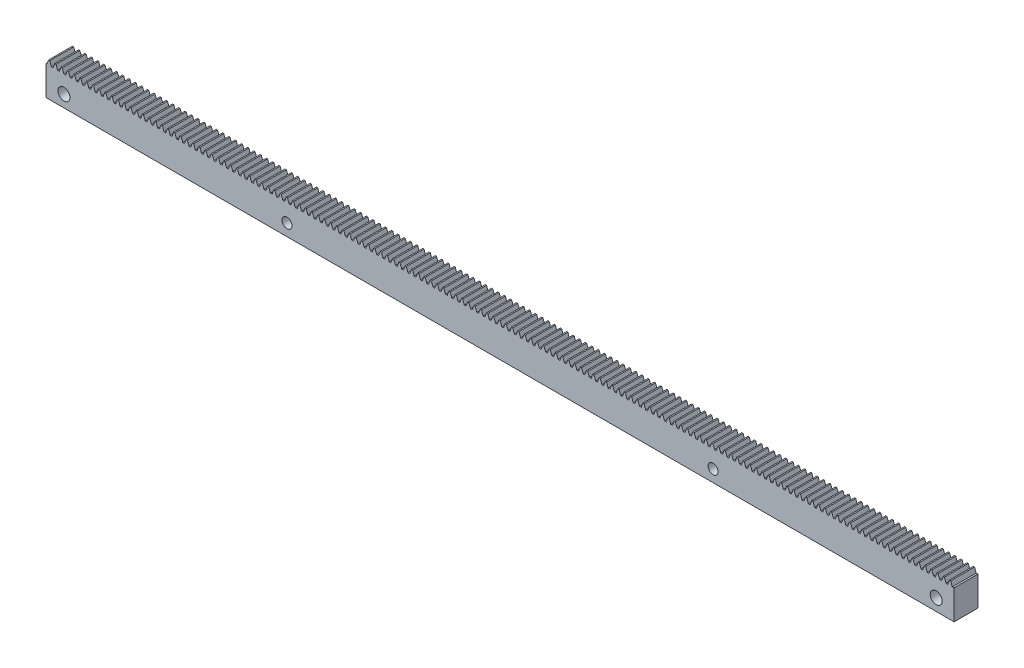
SolidWorks part; units mm, degrees
extrude "Blank" add sketch "BlankSke" against normal blind 6
sketch "BlankSke" plane through (0, 0, 0) normal (0, 0, 1) x (1, 0, 0)
  line L1 (0, 0) -> (228, 0)
  line L2 (0, 0) -> (0, 8.5)
  line L3 (0, 8.5) -> (228, 8.5)
  line L4 (228, 0) -> (228, 8.5)
  dimension "Length" = 228
material "ABS PC"
ref_plane "Plane1" through (0, 0, 0) normal (0, 0, 1) x (1, 0, 0)
ref_plane "Plane2" through (0, 0, 0) normal (0, 1, 0) x (1, 0, 0)
ref_plane "Plane3" through (0, 0, 0) normal (1, 0, 0) x (0, 0, -1)
sketch "HoldingSke" plane through (0, 0, 0) normal (0, 1, 0) x (1, 0, 0)
  line L0 (0, 0) -> (0.2783, 1.9805)
  line L1 (-15, 0) -> (100, 0) construction
  line L2 (0, 0) -> (-2.1039, 2.3779)
  line L3 (0, 0) -> (-11.863, 4.5341)
  line L4 (0, 0) -> (-4.8292, 7.1596)
  line L5 (0, 0) -> (-23.7986, -8.8762)
  line L6 (0, 0) -> (-10.5278, -7.1032)
  line L9 (-71.009, 38.7566) -> (109.412, 104.4245)
  line L10 (-76.2, 2.8779) -> (-68.2, 2.8779)
  line L11 (0, 0) -> (-4, 0)
  line L12 (-76.2, 101.6) -> (-76.181, 101.6)
  line L13 (24.9733, 27.94) -> (52.9518, 28.4284)
  line L14 (24.9733, 27.94) -> (24.9743, 27.94)
  line L15 (24.9733, 27.94) -> (100.4006, 29.5858)
  circle A0 centre (0, 0) radius 19.05
  circle A1 centre (0, 0) radius 4
  circle A2 centre (0, 0) radius 12.7
  dimension "Num_teeth" = 124
  dimension "Width" = 4
  dimension "Pitch_height" = 8
sketch "TooCutSkeIll" plane through (0, 0, 0) normal (0, 0, 1) x (1, 0, 0)
  line L0 (-0.6269, 8.4868) -> (-0.2524, 7.4579)
  line L1 (-0.134, 7.375) -> (0.134, 7.375)
  line L2 (0.2524, 7.4579) -> (0.6269, 8.4868)
  line L3 (228, 8.5) -> (0, 8.5) construction
  line L4 (0, 0) -> (0, 64.897) construction
  line L5 (-13.208, 8) -> (12.954, 8) construction
  line L6 (0, 0) -> (228, 0) construction
  line L7 (0.4497, 8) -> (0.4497, 48.7463) construction
  line L8 (-0.4497, 8) -> (-0.4497, 48.7463) construction
  line L9 (0.6457, 8.5) -> (0.6457, 8.5254)
  line L10 (-0.6457, 8.5) -> (-0.6457, 8.5254)
  line L11 (-0.6457, 8.5254) -> (0.6457, 8.5254)
  arc A0 (0.134, 7.375) -> (0.2524, 7.4579) centre (0.134, 7.501) ccw
  arc A1 (-0.2524, 7.4579) -> (-0.134, 7.375) centre (-0.134, 7.501) ccw
  arc A2 (0.6457, 8.5) -> (0.6269, 8.4868) centre (0.6457, 8.48) ccw
  arc A3 (-0.6269, 8.4868) -> (-0.6457, 8.5) centre (-0.6457, 8.48) ccw
  dimension "Addendum_plus" = 0.5254
  dimension "Pitch_height" = 8
  dimension "Pressure_angle" = 20
  dimension "Gap_width" = 0.8994
  dimension "Dedendum" = 0.625
extrude "ToothCutIll" [suppressed] cut sketch "TooCutSkeIll" against normal through all
sketch "TooCutSkeSim" plane through (0, 0, 0) normal (0, 0, 1) x (1, 0, 0)
  line L0 (0.2222, 7.375) -> (-0.2222, 7.375)
  line L1 (0.6409, 8.5254) -> (0.2222, 7.375)
  line L2 (0, 17.4625) -> (0, 53.467) construction
  line L3 (0.6409, 8.5254) -> (-0.6409, 8.5254)
  line L6 (-0.6409, 8.5254) -> (-0.2222, 7.375)
  line L9 (-0.4497, 8) -> (0.4497, 8) construction
  line L10 (0, 0) -> (228, 0) construction
  line L11 (0.4497, 8) -> (0.4497, 53.467) construction
  line L12 (-0.4497, 8) -> (-0.4497, 53.467) construction
  dimension "Addendum_plus" = 0.5254
  dimension "Pitch_height" = 8
  dimension "Pressure_angle" = 20
  dimension "Gap_width" = 0.8994
  dimension "Dedendum" = 0.625
extrude "ToothCutSim" cut sketch "TooCutSkeSim" against normal through all
pattern_linear "TeethCuts" count 146 spacing 1.5708 along (1, 0, 0) of "ToothCutSim"
sketch "Sketch1" plane through (0, 0, 0) normal (0, 0, 1) x (1, 0, 0)
  line L0 (223.5, 0) -> (223.5, 3) construction
  line L1 (0, 0) -> (228, 0) construction
  line L2 (228, 3) -> (186.6573, 3) construction
  line L3 (228, 0) -> (228, 7.4088) construction
  line L4 (114, 0) -> (114, -6.8538) construction
  line L5 (0, 7.375) -> (0, 0) construction
  line L6 (4.5, 3) -> (223.5, 3) construction
  circle A0 centre (223.5, 3) radius 1.5
  circle A1 centre (4.5, 3) radius 1.5
  circle A2 centre (60.5157, 3) radius 1.25
  circle A3 centre (167.4843, 3) radius 1.25
  dimension "D3" = 3
  dimension "D6" = 3
  dimension "D1" = 3
  dimension "D7" = 2.5
  dimension "D2" = 4.5
  dimension "D4" = 4.5
  dimension "D5" = 3
extrude "Cut-Extrude1" cut sketch "Sketch1" against normal blind 10
equation "' \"Module@HoldingSke\" = 6.35"
equation "' \"Num_teeth@HoldingSke\" = 12"
equation "' \"Ap@HoldingSke\" =  20"
equation "' \"Ap@HoldingSke\" = 20"
equation "' \"Width@HoldingSke\" = 0.25 * 25.4"
equation "' \"Show_teeth@HoldingSke\" = 500"
equation "' \"Backlash@HoldingSke\" = 0.009 * 25.4"
equation "' \"Addendum_fac@HoldingSke\" = 1.0"
equation "' \"Dedendum_fac@HoldingSke\" = 1.25"
equation "' \"Dedendum_add@HoldingSke\" = 0.00005 * 25.4"
equation "' \"Clearance_fac@HoldingSke\" = 0.25"
equation "' \"Pitch_height@HoldingSke\" = 1 * 25.4"
equation "' \"Length@HoldingSke\" = 4.71 * 25.4"
equation "\"Pitch@HoldingSke\" = 1 / \"Module@HoldingSke\""
equation "\"MPH@HoldingSke\" = \"Dedendum_fac@HoldingSke\" / \"Pitch@HoldingSke\" + 2 * \"Dedendum_add@HoldingSke\" + 0.002 * 25.4"
equation "\"MPH@HoldingSke\" = ((sgn( \"MPH@HoldingSke\" - \"Pitch_height@HoldingSke\")+1)*( \"MPH@HoldingSke\" - \"Pitch_height@HoldingSke\"))/2 + \"Pitch_height@HoldingSke\""
equation "\"Blank_height@BlankSke\" = \"Pitch_height@HoldingSke\" + \"Addendum_fac@HoldingSke\"  / \"Pitch@HoldingSke\" "
equation "\"Length@BlankSke\"=\"Length@HoldingSke\"+36"
equation "\"Pressure_angle@TooCutSkeIll\" = \"Ap@HoldingSke\""
equation "\"Addendum_plus@TooCutSkeIll\" =  \"Addendum_fac@HoldingSke\"  / \"Pitch@HoldingSke\" + 0.001 *25.4"
equation "\"Dedendum@TooCutSkeIll\" = \"Dedendum_fac@HoldingSke\"  / \"Pitch@HoldingSke\""
equation "\"Pitch_height@TooCutSkeIll\" =  \"MPH@HoldingSke\""
equation "\"Gap_width@TooCutSkeIll\" = 3.14159265 / 2 / \"Pitch@HoldingSke\" + 6 * \"Backlash@HoldingSke\""
equation "\"Pressure_angle@TooCutSkeSim\" = \"Ap@HoldingSke\""
equation "\"Addendum_plus@TooCutSkeSim\" =  \"Addendum_fac@HoldingSke\"  / \"Pitch@HoldingSke\" + 0.001 * 25.4"
equation "\"Dedendum@TooCutSkeSim\" = \"Dedendum_fac@HoldingSke\"  / \"Pitch@HoldingSke\""
equation "\"Pitch_height@TooCutSkeSim\" =  \"MPH@HoldingSke\""
equation "\"Gap_width@TooCutSkeSim\" = 3.14159265 / 2 / \"Pitch@HoldingSke\" + 6 * \"Backlash@HoldingSke\""
equation "\"Root_fillet@TooCutSkeIll\" = \"Clearance_fac@HoldingSke\" / \"Pitch@HoldingSke\" + \"Dedendum_add@HoldingSke\""
equation "\"Break_rad@TooCutSkeIll\" = 0.02 / \"Pitch@HoldingSke\" * 2"
equation "\"Linear_pitch@TeethCuts\" = 3.14159265 / \"Pitch@HoldingSke\""
equation "\"Num_teeth@HoldingSke\" = int( ( \"Length@HoldingSke\" + 0 ) / (3.14159265 / \"Pitch@HoldingSke\")) + 0.9999  + 1"
equation " \"Num_teeth@TeethCuts\" = ((sgn( \"Num_teeth@TeethCuts\" - \"Num_teeth@HoldingSke\" )-1)*( \"Num_teeth@TeethCuts\" - \"Num_teeth@HoldingSke\" ))/-2+ \"Num_teeth@HoldingSke\""
equation "\"Num_teeth@TeethCuts\"=int( \"Show_teeth@HoldingSke\" ) + 21"
